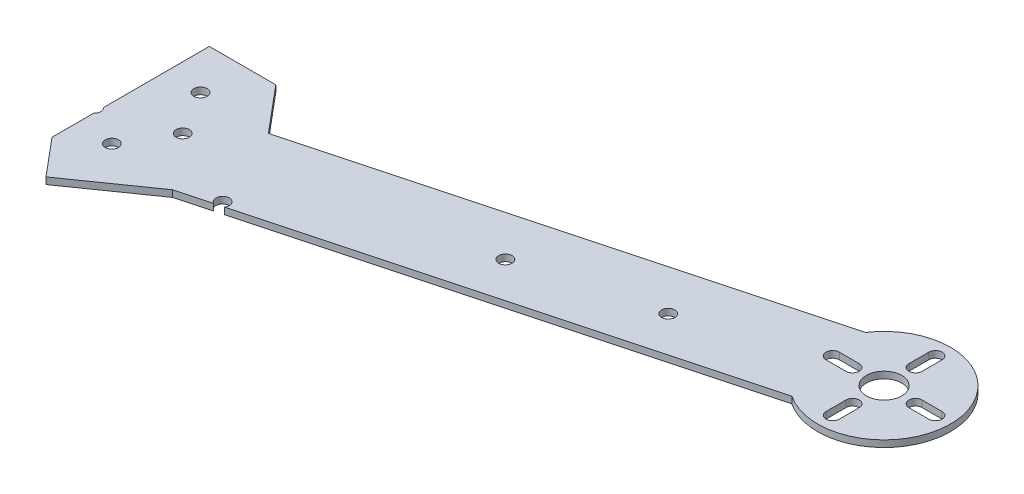
SolidWorks part; units mm, degrees
other "Markup1"
sketch "Sketch5" plane through (0, 1.5, 8.4265) normal (-0.2691, 0.6708, 0.6911) x (0.9345, 0.0084, 0.3557)
ref_plane "Front Plane" through (0, 0, 0) normal (0, 0, 1) x (1, 0, 0)
ref_plane "Top Plane" through (0, 0, 0) normal (0, 1, 0) x (1, 0, 0)
ref_plane "Right Plane" through (0, 0, 0) normal (1, 0, 0) x (0, 0, -1)
sketch "Sketch2" plane through (0, 0, 0) normal (0, 1, 0) x (1, 0, 0)
  line L0 (0, 0) -> (0, 9.382)
  line L1 (0, 35.5) -> (15, 35.5)
  line L2 (15, 35.5) -> (23.6776, 25.1584)
  line L3 (23.6776, 25.1584) -> (129.9295, 53.6285)
  line L4 (0, 0) -> (7.0707, -8.4265)
  line L5 (7.0707, -8.4265) -> (23.8633, 3.3318)
  line L6 (23.8633, 3.3318) -> (134.0979, 32.8636)
  line L7 (23.6776, 25.1584) -> (23.8633, 3.3318) construction
  line L8 (136.0028, 45.3369) -> (147.7774, 45.3369) construction
  line L9 (147.7774, 45.3369) -> (142.4295, 45.3369) construction
  line L10 (142.4295, 45.3369) -> (142.4295, 51.3946) construction
  line L11 (142.4295, 45.3369) -> (142.4295, 39.9998)
  line L12 (135.3295, 45.3369) -> (130.8295, 45.3369) construction
  line L13 (135.3295, 43.8369) -> (130.8295, 43.8369)
  line L14 (135.3295, 46.8369) -> (130.8295, 46.8369)
  line L15 (143.9295, 52.4369) -> (143.9295, 56.9369)
  line L16 (140.9295, 52.4369) -> (140.9295, 56.9369)
  line L17 (142.4295, 52.4369) -> (142.4295, 56.9369) construction
  line L18 (149.5295, 43.8369) -> (154.0295, 43.8369)
  line L19 (149.5295, 46.8369) -> (154.0295, 46.8369)
  line L20 (149.5295, 45.3369) -> (154.0295, 45.3369) construction
  line L21 (140.9295, 38.2369) -> (140.9295, 33.7369)
  line L22 (143.9295, 38.2369) -> (143.9295, 33.7369)
  line L23 (142.4295, 38.2369) -> (142.4295, 33.7369) construction
  line L24 (0, 11.618) -> (0, 35.5)
  arc A0 (134.0979, 32.8636) -> (129.9295, 53.6285) centre (142.4295, 45.3369) ccw
  circle A1 centre (142.4295, 45.3369) radius 4
  arc A2 (135.3295, 43.8369) -> (135.3295, 46.8369) centre (135.3295, 45.3369) ccw
  arc A3 (130.8295, 46.8369) -> (130.8295, 43.8369) centre (130.8295, 45.3369) ccw
  arc A4 (140.9295, 52.4369) -> (143.9295, 52.4369) centre (142.4295, 52.4369) ccw
  arc A5 (143.9295, 56.9369) -> (140.9295, 56.9369) centre (142.4295, 56.9369) ccw
  arc A6 (149.5295, 46.8369) -> (149.5295, 43.8369) centre (149.5295, 45.3369) ccw
  arc A7 (154.0295, 43.8369) -> (154.0295, 46.8369) centre (154.0295, 45.3369) ccw
  arc A8 (143.9295, 38.2369) -> (140.9295, 38.2369) centre (142.4295, 38.2369) ccw
  arc A9 (140.9295, 33.7369) -> (143.9295, 33.7369) centre (142.4295, 33.7369) ccw
  circle A10 centre (8, 25.5) radius 1.5
  circle A11 centre (14, 15.5) radius 1.5
  circle A12 centre (8, 5.5) radius 1.5
  arc A13 (0, 9.382) -> (0, 11.618) centre (-1, 10.5) ccw
  point P17 (133.0795, 45.3369)
  point P27 (142.4295, 54.6869)
  point P34 (151.7795, 45.3369)
  point P41 (142.4295, 35.9869)
  point P46 (142.4295, 45.3369)
  dimension "D8" = 3
  dimension "D16" = 8
  dimension "D17" = 4.5
  dimension "D21" = 8
  dimension "D22" = 3
  dimension "D23" = 10
  dimension "D24" = 14
  dimension "D25" = 3
  dimension "D26" = 20
  dimension "D27" = 3
  dimension "D28" = 30
  dimension "D29" = 3
  dimension "D30" = 15
  dimension "D1" = 35.5
  dimension "D2" = 15
  dimension "D3" = 13.5
  dimension "D4" = 130
  dimension "D5" = 110
  dimension "D6" = 115
  dimension "D7" = 12.5
  dimension "D9" = 15
  dimension "D10" = 11
  dimension "D11" = 140
  dimension "D12" = 95
  dimension "D13" = 20.5
  dimension "D14" = 75.49
  dimension "D15" = 104.513
  dimension "D18" = 7.1
  dimension "D20" = 23.2
  dimension "D31" = 15
  dimension "D19" = 4
extrude "Boss-Extrude1" add sketch "Sketch2" along normal blind 1.5 contours A13 L0 L4 L5 L6 A0 L3 L2 L1 L24 A12 A11 A10 A9 L21 A8 L22 A7 L18 A6 L19 A5 L15 A4 L16 A3 L14 A2 L13 A1 region at (71.7252, 0, -27.9412)
sketch "Sketch3" plane through (0, 1.5, 0) normal (0, 1, 0) x (1, 0, 0)
  circle A0 centre (31.86, 6.64) radius 1.5
  circle A1 centre (14, 15.5) radius 1.5 construction
  point P4 (32, 8.8291)
  dimension "D1" = 3
  dimension "D2" = 17.86
  dimension "D3" = 8.86
extrude "Cut-Extrude1" cut sketch "Sketch3" against normal up to surface (1.5 mm away) up to face at (35.9261, 0, -20.3599)
sketch "Sketch4" plane through (0, 1.5, 0) normal (0, 1, 0) x (1, 0, 0)
  line L0 (142.4295, 45.3369) -> (23.572, 13.4892) construction
  line L1 (23.6776, 25.1584) -> (129.9295, 53.6285) construction
  circle A0 centre (75.0373, 27.2793) radius 1.5
  circle A1 centre (104.0151, 35.0438) radius 1.5
  point P11 (77.49, 27.9365)
  point P12 (108.0366, 36.1214)
  point P13 (75.0373, 27.2793)
  dimension "D1" = 30
  dimension "D2" = 3
  dimension "D3" = 3
extrude "Cut-Extrude2" cut sketch "Sketch4" against normal up to surface (1.5 mm away) up to face at (35.2404, 0, -18.1033)
